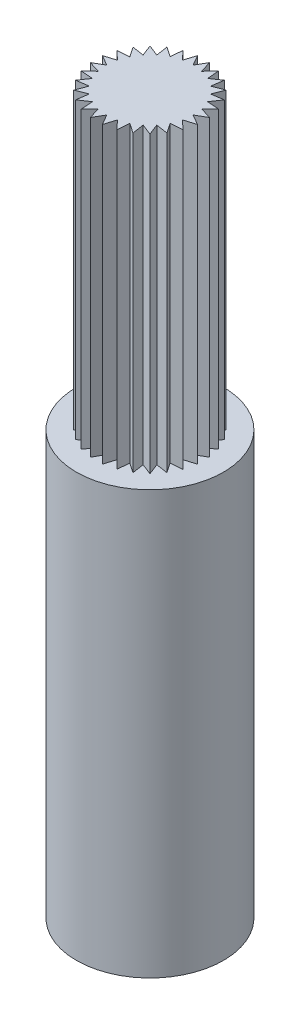
SolidWorks part; units mm, degrees
ref_plane "Front Plane" through (0, 0, 0) normal (0, 0, 1) x (1, 0, 0)
ref_plane "Top Plane" through (0, 0, 0) normal (0, 1, 0) x (1, 0, 0)
ref_plane "Right Plane" through (0, 0, 0) normal (1, 0, 0) x (0, 0, -1)
sketch "Sketch1" plane through (0, 0, 0) normal (0, 1, 0) x (1, 0, 0)
  line L0 (-1.8555, -1.6783) -> (1.8555, -1.6783)
  circle A0 centre (0, 0) radius 3.175
  arc A1 (1.8555, -1.6783) -> (-1.8555, -1.6783) centre (0, 0) ccw
  dimension "D1" = 6.35
  dimension "D2" = 5.0038
  dimension "D3" = 3.711
extrude "Boss-Extrude1" add sketch "Sketch1" along normal blind 18
sketch "Sketch2" plane through (0, 18, 0) normal (0, 1, 0) x (1, 0, 0)
  circle A0 centre (0, 0) radius 3.175
extrude "Boss-Extrude2" add sketch "Sketch2" along normal blind 0.254
sketch "Sketch4" plane through (0, 18.254, 0) normal (0, 1, 0) x (1, 0, 0)
  circle A0 centre (0, 0) radius 3.175
  dimension "D1" = 6.35
extrude "Boss-Extrude3" add sketch "Sketch4" along normal blind 12.7
sketch "Sketch5" plane through (0, 30.954, 0) normal (0, 1, 0) x (1, 0, 0)
  line L0 (0, 0) -> (0, 3.175) construction
  line L1 (0, 1.8625) -> (0.7112, 3.0943)
  line L2 (0, 1.8625) -> (-0.7112, 3.0943)
  arc A0 (0.7112, 3.0943) -> (-0.7112, 3.0943) centre (0, 0) ccw
  dimension "D1" = 6.35
  dimension "D2" = 1.4224
  dimension "D3" = 30
extrude "Cut-Extrude2" cut sketch "Sketch5" against normal blind 12.7
pattern_circular "CirPattern1" count 28 over 360 about axis through (0, 30.954, 0) along (0, 1, 0) of "Cut-Extrude2"
